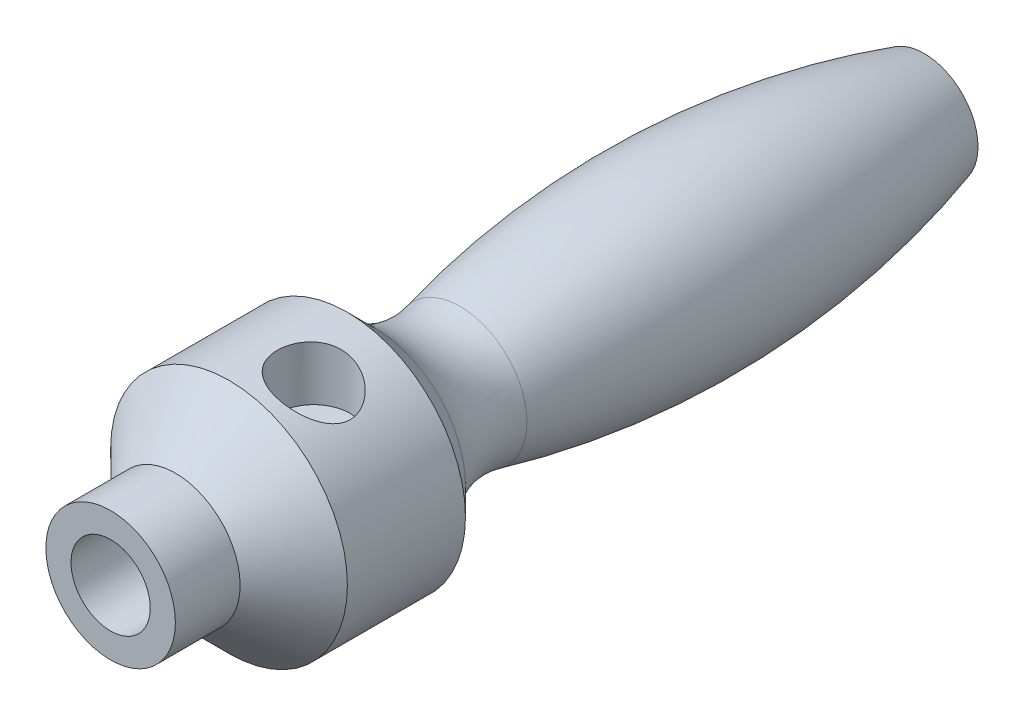
SolidWorks part; units mm, degrees
ref_plane "Top Plane" through (0, 0, 0) normal (0, 0, 1) x (1, 0, 0)
ref_plane "Front Plane" through (0, 0, 0) normal (0, 1, 0) x (1, 0, 0)
ref_plane "Right Plane" through (0, 0, 0) normal (1, 0, 0) x (0, 0, -1)
sketch "Sketch1" plane through (0, 0, 0) normal (0, 1, 0) x (1, 0, 0)
  line L0 (4.35, 0) -> (7.1108, 0)
  line L1 (7.1108, 0) -> (7.1108, 7.1108)
  line L2 (7.1108, 7.1108) -> (13, 13)
  line L3 (13, 13) -> (13, 25.9662)
  line L4 (13, 25.9662) -> (9.9922, 28.974)
  line L5 (5.9062, 33.06) -> (5.9062, 89.3427) construction
  line L6 (5.9062, 89.3427) -> (0, 89.3427)
  line L7 (4.35, 0) -> (4.35, 24.5)
  line L8 (4.35, 24.5) -> (0, 24.5)
  line L9 (0, 24.5) -> (0, 89.3427)
  line L10 (0, 0) -> (0, 24.5) construction
  arc A0 (7.3384, 38.3748) -> (5.9062, 89.3427) centre (-87.9445, 61.2013) ccw
  arc A1 (9.9922, 28.974) -> (7.3384, 38.3748) centre (17.0632, 36.0451) cw
  dimension "D2" = 10
  dimension "D1" = 4.35
  dimension "D3" = 24.5
  dimension "D4" = 89.3427
  dimension "D5" = 13
  dimension "D6" = 13
revolve "Revolve1" add sketch "Sketch1" angle 360 about L10
sketch "Sketch2" plane through (0, 0, 0) normal (0, 1, 0) x (1, 0, 0)
  line L0 (3.8, 18.5) -> (0, 0) construction
  line L1 (0, 0) -> (0, 18.5) construction
  line L2 (0, 18.5) -> (3.8, 18.5) construction
  circle A0 centre (3.8, 18.5) radius 1.5
  dimension "D1" = 3
  dimension "D2" = 18.5
  dimension "D3" = 3.8
extrude "Cut-Extrude1" cut sketch "Sketch2" along normal through all and the other way blind 5
sketch "Sketch3" plane through (0, -5, 0) normal (0, 1, 0) x (1, 0, 0)
  circle A0 centre (3.8, 18.5) radius 4
  dimension "D1" = 8
extrude "Cut-Extrude2" cut sketch "Sketch3" along normal blind 18 from offset 12
